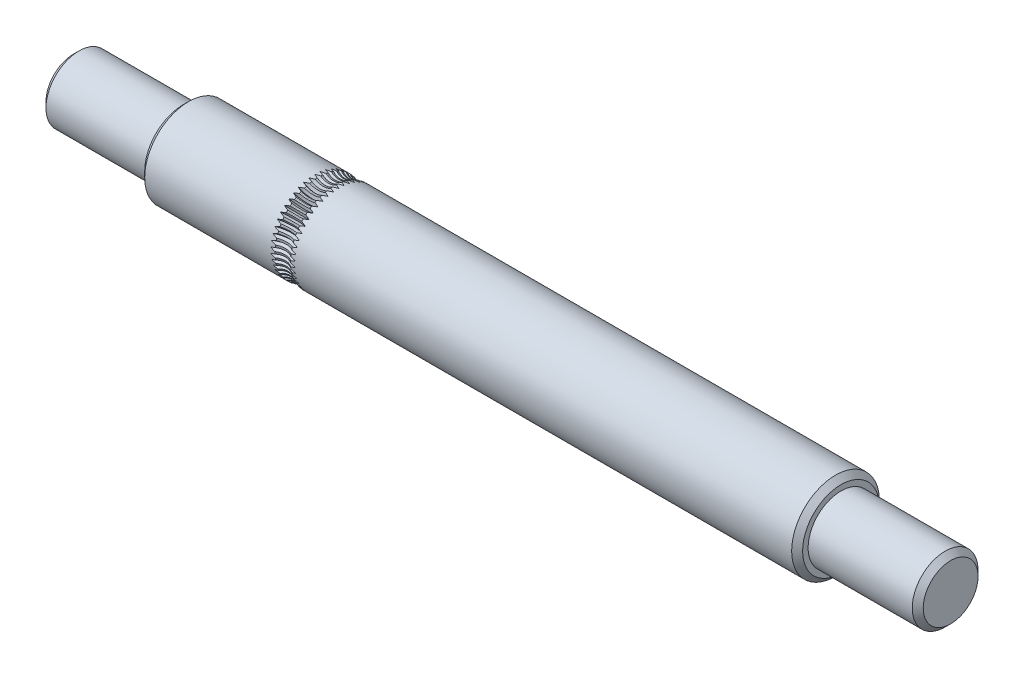
SolidWorks part; units mm, degrees
material "Plain Carbon Steel"
ref_plane "Front Plane" through (0, 0, 0) normal (0, 0, 1) x (1, 0, 0)
ref_plane "Top Plane" through (0, 0, 0) normal (0, 1, 0) x (1, 0, 0)
ref_plane "Right Plane" through (0, 0, 0) normal (1, 0, 0) x (0, 0, -1)
sketch "Sketch1" plane through (0, 0, 0) normal (0, 0, 1) x (1, 0, 0)
  line L0 (-13.1, 4) -> (46.9, 4)
  line L1 (-13.1, 3) -> (-23.1, 3)
  line L2 (-23.1, 0) -> (56.9, 0)
  line L3 (-13.1, 3) -> (-13.1, 4)
  line L4 (-23.1, 3) -> (-23.1, 0)
  line L5 (56.9, 0) -> (56.9, 3)
  line L6 (46.9, 4) -> (46.9, 3)
  line L7 (46.9, 3) -> (56.9, 3)
  line L8 (0, 0) -> (67.2135, 0) construction
  line L9 (0, 0) -> (0, 19.6593) construction
  dimension "D1" = 8
  dimension "D2" = 60
  dimension "D3" = 13.1
  dimension "D4" = 10
  dimension "D5" = 6
  dimension "D6" = 10
revolve "Revolve1" add sketch "Sketch1" angle 360 about L8
chamfer "Chamfer1" distance 0.5 angle 45 4 edges at (56.9, 0, 3) (46.9, 0, 4) (-13.1, 0, 4) (-23.1, 0, 3)
sketch "Sketch2" plane through (0, 0, 0) normal (1, 0, 0) x (0, 0, -1)
  line L0 (0, 0) -> (0, 5) construction
  line L1 (9.9899, 5) -> (-9.864, 5) construction
  line L2 (0.1562, 3.7705) -> (0, 3.5)
  line L3 (0, 3.5) -> (-0.1562, 3.7705)
  line L4 (-1.3354, 5) -> (1.3354, 5)
  line L5 (-0.1562, 3.7705) -> (-1.3354, 3.7705)
  line L6 (0.1562, 3.7705) -> (1.3354, 3.7705)
  line L7 (1.3354, 3.7705) -> (1.3354, 5)
  line L8 (-1.3354, 3.7705) -> (-1.3354, 5)
  line L9 (0, 0) -> (-6.9817, 0) construction
  line L10 (5.645, 4) -> (-5.97, 4) construction
  circle A0 centre (0, 0) radius 4 construction
  circle A1 centre (0, 0) radius 3.5 construction
  dimension "D5" = 5
  dimension "D1" = 60
  dimension "D2" = 3
  dimension "D3" = 2.459
  dimension "D4" = 1
revolve "Cut-Revolve1" cut sketch "Sketch2" angle 360 about L1
pattern_circular "CirPattern1" count 50 over 360 about axis through (0, 0, 0) along (-1, 0, 0) of "Cut-Revolve1"
sketch "Sketch3" plane through (0, 0, 0) normal (0, 0, 1) x (1, 0, 0)
  line L0 (56.4, 3) -> (46.9, 3) construction
  line L1 (8, 4) -> (0.75, 4)
  line L2 (8, 4) -> (8, 3)
  line L3 (8, 3) -> (0.75, 3)
  line L4 (0.75, 4) -> (0.75, 3)
  line L5 (-0.75, 4) -> (-8, 4)
  line L6 (-0.75, 4) -> (-0.75, 3)
  line L7 (-0.75, 3) -> (-8, 3)
  line L8 (-8, 4) -> (-8, 3)
  line L9 (0, 0) -> (0, 15.3026) construction
  line L10 (0, 0) -> (-13.7134, 0) construction
  line L11 (46.4, 4) -> (1.118, 4) construction
  dimension "D1" = 1.5
  dimension "D2" = 16
revolve "Cut-Revolve2" [suppressed] cut sketch "Sketch3" angle 360 about L10
